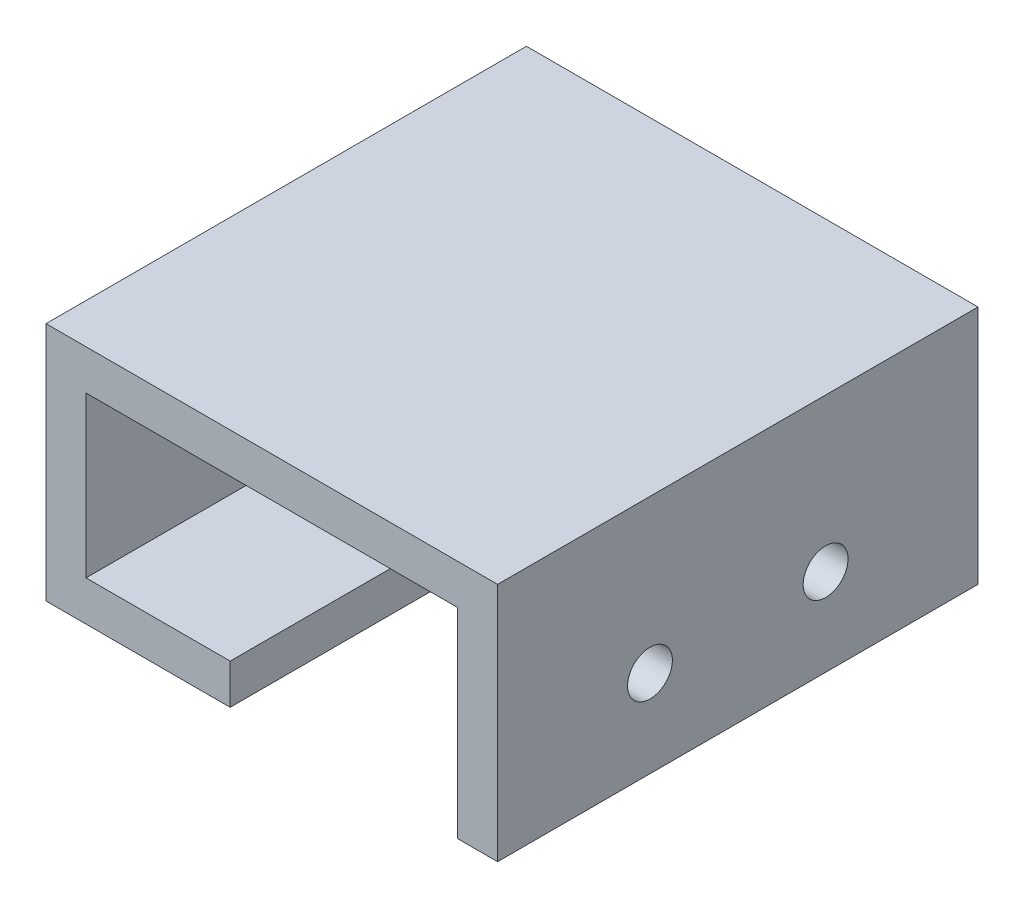
SolidWorks part; units mm, degrees
ref_plane "Front Plane" through (0, 0, 0) normal (0, 0, 1) x (1, 0, 0)
ref_plane "Top Plane" through (0, 0, 0) normal (0, 1, 0) x (1, 0, 0)
ref_plane "Right Plane" through (0, 0, 0) normal (1, 0, 0) x (0, 0, -1)
sketch "Sketch1" plane through (0, 0, 0) normal (0, 0, 1) x (1, 0, 0)
  line L0 (0, 0) -> (0, 19.05)
  line L1 (0, 19.05) -> (-35.814, 19.05)
  line L2 (-35.814, 19.05) -> (-35.814, 0)
  line L3 (-35.814, 0) -> (-21.209, 0)
  line L4 (-21.209, 0) -> (-21.209, 3.175)
  line L5 (-21.209, 3.175) -> (-32.639, 3.175)
  line L6 (-32.639, 3.175) -> (-32.639, 15.875)
  line L7 (-32.639, 15.875) -> (-3.175, 15.875)
  line L8 (-3.175, 15.875) -> (-3.175, 0)
  line L9 (-3.175, 0) -> (0, 0)
  dimension "D1" = 35.814
  dimension "D2" = 19.05
  dimension "D3" = 3.175
  dimension "D4" = 3.175
  dimension "D5" = 3.175
  dimension "D6" = 3.175
  dimension "D7" = 11.43
extrude "Boss-Extrude1" add sketch "Sketch1" against normal blind 38.1
sketch "Sketch2" plane through (0, 0, 0) normal (1, 0, 0) x (0, 0, -1)
  line L0 (38.1, 0) -> (38.1, 19.05) construction
  line L1 (0, 0) -> (0, 19.05) construction
  line L2 (38.1, 0) -> (0, 0) construction
  circle A0 centre (26.0141, 6.9139) radius 1.778
  circle A1 centre (12.0859, 6.9139) radius 1.778
  dimension "D2" = 3.556
  dimension "D4" = 3.556
  dimension "D1" = 12.0859
  dimension "D3" = 12.0859
  dimension "D5" = 6.9139
  dimension "D6" = 6.9139
extrude "Cut-Extrude1" cut sketch "Sketch2" against normal blind 15.24 contours A1 | A0 | A1 | A0 region at (0, 6.9139, -26.0141) region at (0, 6.9139, -12.0859)
sketch "Sketch3" plane through (0, 0, 0) normal (0, -1, 0) x (-1, 0, 0)
  line L0 (35.814, 38.1) -> (21.209, 38.1) construction
  line L1 (35.814, 38.1) -> (35.814, 0) construction
  circle A0 centre (26.543, 19.05) radius 1.778
  dimension "D3" = 3.556
  dimension "D1" = 19.05
  dimension "D2" = 9.271
extrude "Cut-Extrude2" cut sketch "Sketch3" against normal blind 15.24
